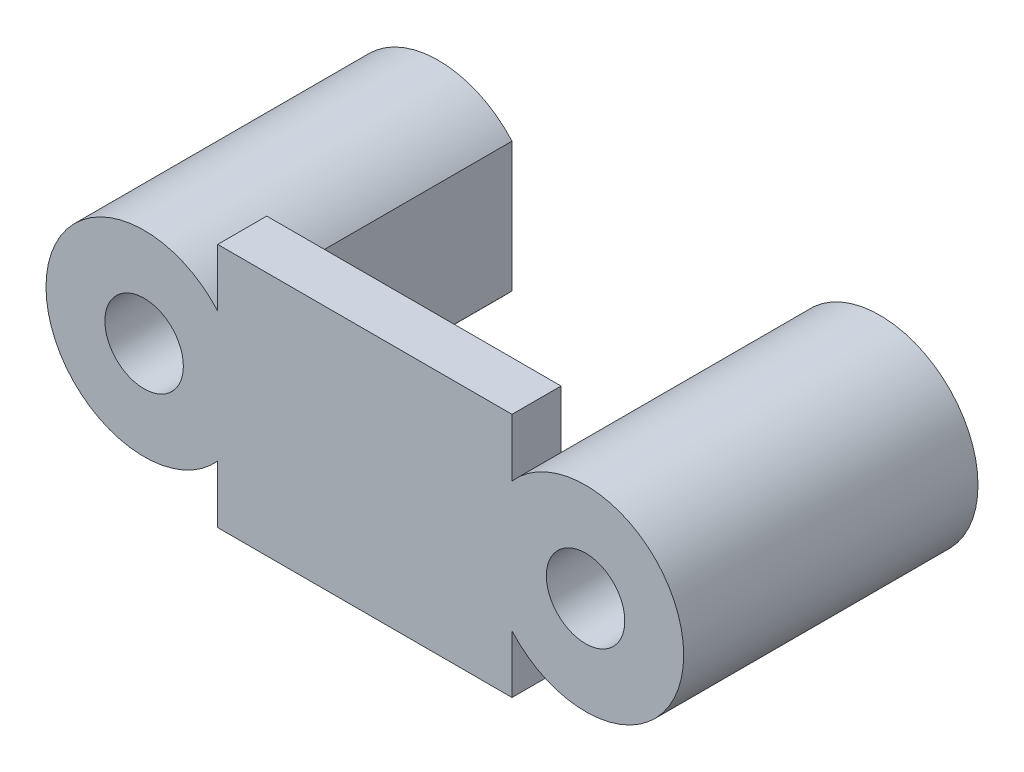
SolidWorks part; units mm, degrees
ref_plane "Ebene vorne" through (0, 0, 0) normal (0, 0, 1) x (1, 0, 0)
ref_plane "Ebene oben" through (0, 0, 0) normal (0, 1, 0) x (1, 0, 0)
ref_plane "Ebene rechts" through (0, 0, 0) normal (1, 0, 0) x (0, 0, -1)
sketch "Skizze2" plane through (0, 0, 0) normal (0, 0, 1) x (1, 0, 0)
  line L0 (0, 0) -> (0, 4.16) construction
  line L1 (9, 0) -> (-9, 0) construction
  line L2 (-6, -2.6458) -> (-6, -5)
  line L7 (6, 5) -> (-6, 5)
  line L8 (6, 5) -> (6, 2.6458)
  line L9 (6, -5) -> (-6, -5)
  line L10 (-6, 5) -> (-6, 2.6458)
  line L11 (6, 5) -> (-6, -5) construction
  line L12 (6, -5) -> (-6, 5) construction
  line L13 (6, -2.6458) -> (6, -5)
  circle A0 centre (-9, 0) radius 1.6
  arc A1 (-6, 2.6458) -> (-6, -2.6458) centre (-9, 0) ccw
  circle A2 centre (9, 0) radius 1.6
  arc A3 (6, 2.6458) -> (6, -2.6458) centre (9, 0) cw
  dimension "D1" = 3.2
  dimension "D2" = 8
  dimension "D3" = 18
  dimension "D4" = 10
  dimension "D5" = 12
extrude "Aufsatz-Linear austragen1" add sketch "Skizze2" along normal blind 12
ref_plane "Ebene1" through (0, 0, 0) normal (0, -1, 0) x (-1, 0, 0)
sketch "Skizze3" plane through (0, 0, 0) normal (0, -1, 0) x (-1, 0, 0)
  line L0 (6, 0) -> (-6, 0) construction
  line L1 (-6, 0) -> (6, 0)
  line L2 (-6, 0) -> (-6, -10)
  line L3 (-6, -10) -> (6, -10)
  line L4 (6, 0) -> (6, -10)
  line L5 (0, -10) -> (0, 0) construction
  dimension "D1" = 10
  dimension "D2" = 12
extrude "Schnitt-Linear austragen1" cut sketch "Skizze3" against normal through all and the other way through all
